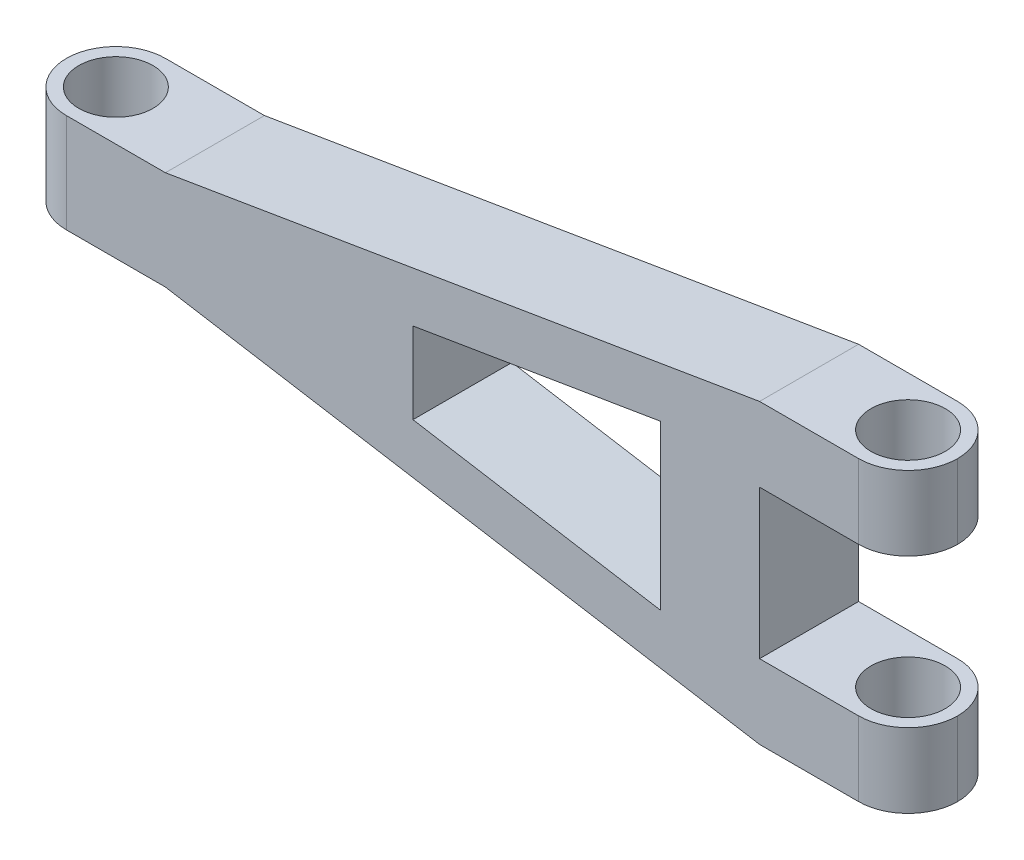
SolidWorks part; units mm, degrees
ref_plane "Plane1" through (0, 0, 0) normal (0, 0, 1) x (1, 0, 0)
ref_plane "Plane2" through (0, 0, 0) normal (0, 1, 0) x (1, 0, 0)
ref_plane "Plane3" through (0, 0, 0) normal (1, 0, 0) x (0, 0, -1)
other "Configuration Table"
sketch "Sketch1" plane through (0, 0, 0) normal (0, 0, 1) x (1, 0, 0)
  line L0 (-80, 15) -> (-50, 15)
  line L1 (-80, 15) -> (-80, -5)
  line L2 (-50, -5) -> (-80, -5)
  line L4 (100, -10) -> (70, -10)
  line L5 (100, -10) -> (100, -25)
  line L6 (70, -25) -> (100, -25)
  line L7 (50, 21.5287) -> (0, 13.1954)
  line L8 (100, 20) -> (70, 20)
  line L9 (100, 20) -> (100, 35)
  line L10 (70, 35) -> (100, 35)
  line L11 (0, -3.1954) -> (50, -11.5287)
  line L12 (70, 35) -> (-50, 15)
  line L13 (70, -25) -> (-50, -5)
  line L14 (70, 20) -> (70, -10)
  line L15 (50, 21.5287) -> (50, -11.5287)
  line L16 (0, 13.1954) -> (0, -3.1954)
  point P12 (-80, 5)
  point P13 (70, 5)
  dimension "D1" = 20
  dimension "D2" = 30
  dimension "D3" = 60
  dimension "D4" = 30
  dimension "D5" = 180
  dimension "D6" = 30
  dimension "D7" = 10
  dimension "D8" = 20
  dimension "D9" = 50
extrude "Base-Extrude" add sketch "Sketch1" along normal blind 20
fillet "Fillet1" radius 10 6 edges at (100, -17.5, 20) (100, -17.5, 0) (100, 27.5, 0) (100, 27.5, 20) (-80, 5, 0) (-80, 5, 20)
sketch "Sketch2" plane through (0, 0, 0) normal (0, 1, 0) x (1, 0, 0)
  circle A0 centre (90, -10) radius 7.5
  circle A1 centre (-70, -10) radius 7.5
  arc A2 (90, -20) -> (100, -10) centre (90, -10) ccw construction
  arc A3 (-80, -10) -> (-70, -20) centre (-70, -10) ccw construction
  dimension "D1" = 15
  dimension "D2" = 15
extrude "Cut-Extrude1" cut sketch "Sketch2" against normal through all and the other way through all
